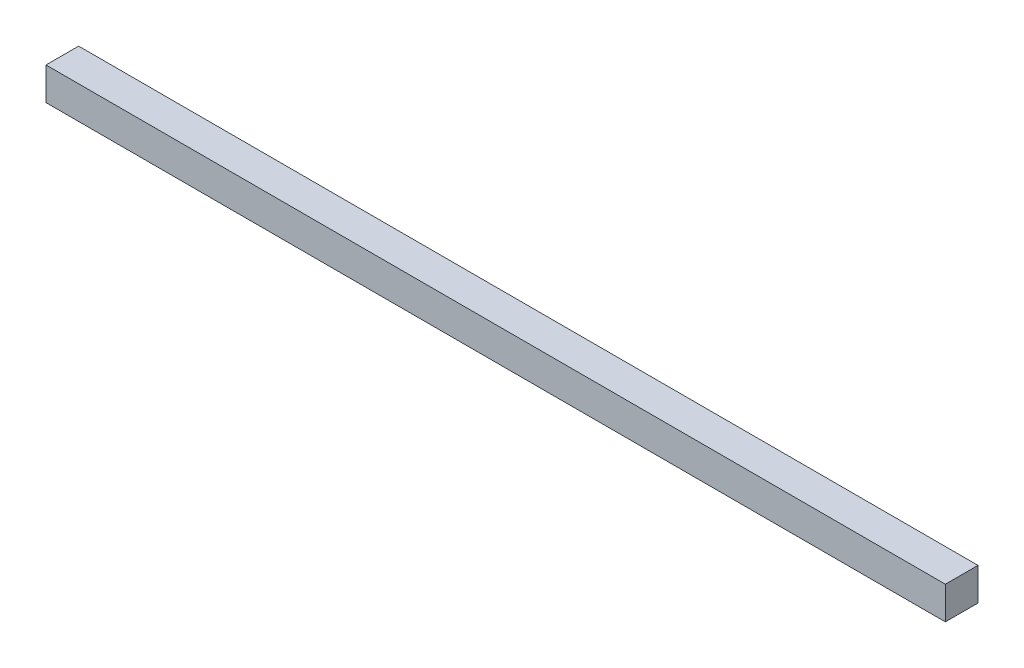
SolidWorks part; units mm, degrees
ref_plane "Front Plane" through (0, 0, 0) normal (0, 0, 1) x (1, 0, 0)
ref_plane "Top Plane" through (0, 0, 0) normal (0, 1, 0) x (1, 0, 0)
ref_plane "Right Plane" through (0, 0, 0) normal (1, 0, 0) x (0, 0, -1)
sketch "Sketch1" plane through (0, 0, 0) normal (0, 0, 1) x (1, 0, 0)
  line L0 (-124, 0) -> (124, 0) construction
  point P3 (0, 0)
  point P4 (0, 0)
  dimension "D1" = 248
sketch "Sketch2" plane through (0, 0, 0) normal (1, 0, 0) x (0, 0, -1)
  line L1 (-4.5, -4.5) -> (4.5, -4.5)
  line L2 (-4.5, -4.5) -> (-4.5, 4.5)
  line L3 (-4.5, 4.5) -> (4.5, 4.5)
  line L4 (4.5, -4.5) -> (4.5, 4.5)
  line L5 (-4.5, -4.5) -> (4.5, 4.5) construction
  line L6 (-4.5, 4.5) -> (4.5, -4.5) construction
  point P0 (0, 0)
  dimension "D1" = 9
extrude "Boss-Extrude1" add sketch "Sketch2" against normal up to vertex (124 mm away) and the other way up to vertex (124 mm away) up to point (-124, 0, 0) other way up to point (124, 0, 0)
